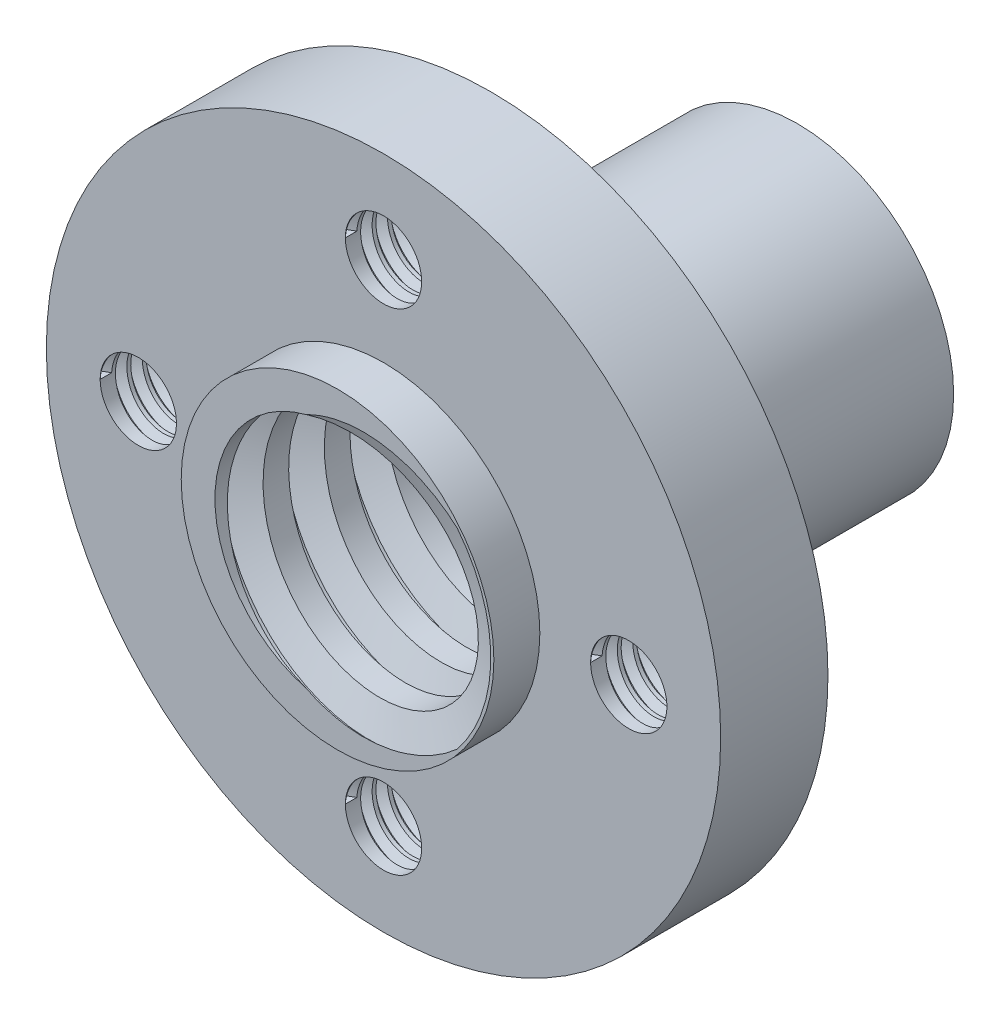
SolidWorks part; units mm, degrees
material "Brass"
ref_plane "Front Plane" through (0, 0, 0) normal (0, 0, 1) x (1, 0, 0)
ref_plane "Top Plane" through (0, 0, 0) normal (0, 1, 0) x (1, 0, 0)
ref_plane "Right Plane" through (0, 0, 0) normal (1, 0, 0) x (0, 0, -1)
sketch "Sketch1" plane through (0, 0, 0) normal (0, 0, 1) x (1, 0, 0)
  circle A0 centre (0, 0) radius 11
  circle A1 centre (0, 0) radius 5.1
  circle A2 centre (0, 0) radius 8 construction
  circle A3 centre (0, 8) radius 1.2446
  circle A4 centre (8, 0) radius 1.2446
  circle A5 centre (0, -8) radius 1.2446
  circle A6 centre (-8, 0) radius 1.2446
  point P16 (0, 0)
  dimension "D1" = 22
  dimension "D2" = 10.2
  dimension "D3" = 16
  dimension "D4" = 2.4892
  dimension "D5" = 4
extrude "Boss-Extrude1" add sketch "Sketch1" against normal blind 3.5
sketch "Sketch2" plane through (0, 0, 0) normal (0, 0, 1) x (1, 0, 0)
  circle A0 centre (0, 0) radius 5.1
  circle A1 centre (0, 0) radius 4
  dimension "D1" = 8
extrude "Boss-Extrude2" add sketch "Sketch2" along normal blind 1.5 and the other way blind 13.5
sketch "Sketch3" plane through (0, 0, 1.5) normal (0, 0, 1) x (1, 0, 0)
  circle A0 centre (0, 0) radius 4
curve "Helix/Spiral1" pitch 2 height 15 turns 7.5
sketch "Sketch4" plane through (0, 0, 0) normal (0, 1, 0) x (1, 0, 0)
  line L0 (3, -0.55) -> (3, -2.45)
  line L1 (3, -2.45) -> (5, -1.7146)
  line L2 (5, -1.7146) -> (5, -1.2854)
  line L3 (5, -1.2854) -> (3, -0.55)
  line L4 (3, -1.5) -> (5, -1.5)
  point P6 (4, -1.5)
  dimension "D1" = 1.9
  dimension "D2" = 2
  dimension "D3" = 69.811
sweep "Cut-Sweep1" cut profiles "Sketch4" path "Helix/Spiral1"
fillet "Fillet2" [suppressed] radius 0.3
thread "Thread1" pitch 0.5 profile "Thread Profile1" start angle 0, offset 0, length 0, pitch 0.5, diameter 2.4892
ref_plane "Plane1" through (6.7554, 0, 0) normal (0, -1, 0) x (-1, 0, 0)
sketch "Thread Profile1" plane through (6.7554, 0, 0) normal (0, -1, 0) x (-1, 0, 0)
  line L0 (0, 0) -> (0, 0.5) construction
  line L1 (0, 0) -> (0.2706, 0.1562)
  line L2 (0.2706, 0.1562) -> (0.2706, 0.2187)
  line L3 (0.2706, 0.2187) -> (0, 0.375)
  line L4 (0.2706, 0.1875) -> (0, 0.1875) construction
  line L11 (0, 0) -> (0, 0.375)
  point P2 (0, 0)
  dimension "Pitch" = 0.5
  dimension "Profile_Angle" = 60
  dimension "Profile_Land" = 0.0625
  dimension "Profile_Height" = 0.2706
thread "Thread2" pitch 0.5 profile "Thread Profile2" start angle 0, offset 0, length 0, pitch 0.5, diameter 2.4892
ref_plane "Plane2" through (-1.2446, 8, 0) normal (0, -1, 0) x (-1, 0, 0)
sketch "Thread Profile2" plane through (-1.2446, 8, 0) normal (0, -1, 0) x (-1, 0, 0)
  line L0 (0, 0) -> (0, 0.5) construction
  line L1 (0, 0) -> (0.2706, 0.1562)
  line L2 (0.2706, 0.1562) -> (0.2706, 0.2187)
  line L3 (0.2706, 0.2187) -> (0, 0.375)
  line L4 (0.2706, 0.1875) -> (0, 0.1875) construction
  line L11 (0, 0) -> (0, 0.375)
  point P2 (0, 0)
  dimension "Pitch" = 0.5
  dimension "Profile_Angle" = 60
  dimension "Profile_Land" = 0.0625
  dimension "Profile_Height" = 0.2706
thread "Thread3" pitch 0.5 profile "Thread Profile3" start angle 0, offset 0, length 0, pitch 0.5, diameter 2.4892
ref_plane "Plane3" through (-9.2446, 0, 0) normal (0, -1, 0) x (-1, 0, 0)
sketch "Thread Profile3" plane through (-9.2446, 0, 0) normal (0, -1, 0) x (-1, 0, 0)
  line L0 (0, 0) -> (0, 0.5) construction
  line L1 (0, 0) -> (0.2706, 0.1562)
  line L2 (0.2706, 0.1562) -> (0.2706, 0.2187)
  line L3 (0.2706, 0.2187) -> (0, 0.375)
  line L4 (0.2706, 0.1875) -> (0, 0.1875) construction
  line L11 (0, 0) -> (0, 0.375)
  point P2 (0, 0)
  dimension "Pitch" = 0.5
  dimension "Profile_Angle" = 60
  dimension "Profile_Land" = 0.0625
  dimension "Profile_Height" = 0.2706
thread "Thread4" pitch 0.5 profile "Thread Profile4" start angle 0, offset 0, length 0, pitch 0.5, diameter 2.4892
ref_plane "Plane4" through (-1.2446, -8, 0) normal (0, -1, 0) x (-1, 0, 0)
sketch "Thread Profile4" plane through (-1.2446, -8, 0) normal (0, -1, 0) x (-1, 0, 0)
  line L0 (0, 0) -> (0, 0.5) construction
  line L1 (0, 0) -> (0.2706, 0.1562)
  line L2 (0.2706, 0.1562) -> (0.2706, 0.2187)
  line L3 (0.2706, 0.2187) -> (0, 0.375)
  line L4 (0.2706, 0.1875) -> (0, 0.1875) construction
  line L11 (0, 0) -> (0, 0.375)
  point P2 (0, 0)
  dimension "Pitch" = 0.5
  dimension "Profile_Angle" = 60
  dimension "Profile_Land" = 0.0625
  dimension "Profile_Height" = 0.2706
